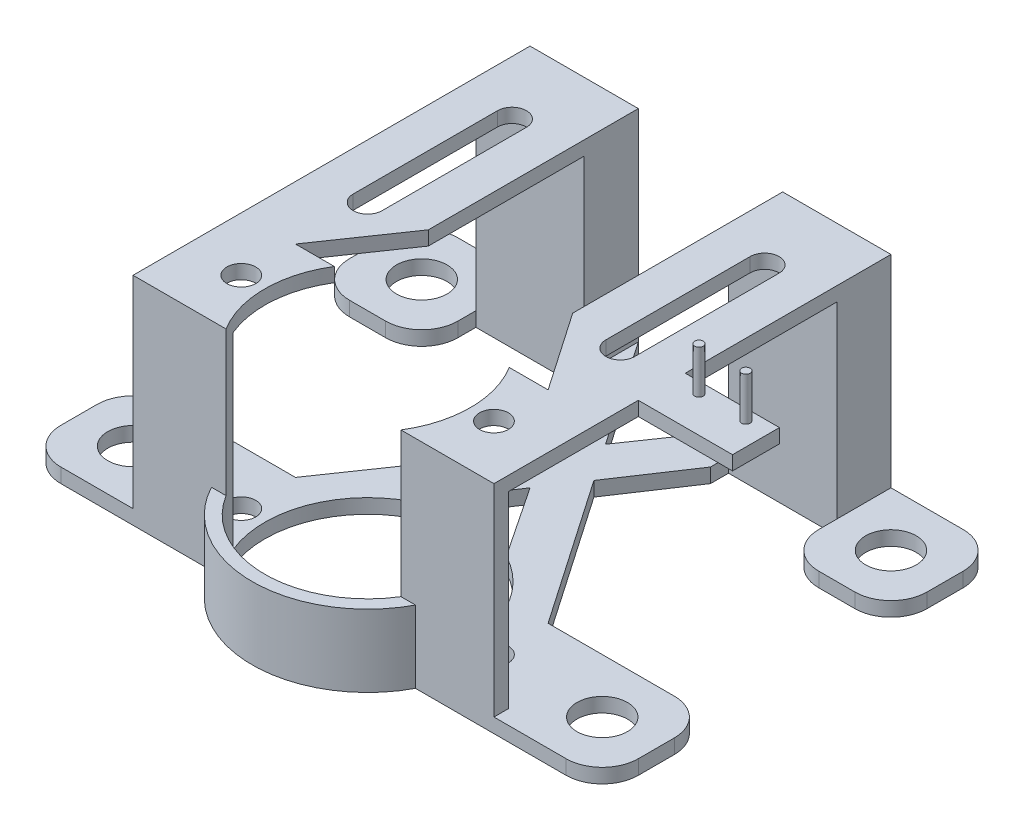
SolidWorks part; units mm, degrees
ref_plane "Front Plane" through (0, 0, 0) normal (0, 0, 1) x (1, 0, 0)
ref_plane "Top Plane" through (0, 0, 0) normal (0, 1, 0) x (1, 0, 0)
ref_plane "Right Plane" through (0, 0, 0) normal (1, 0, 0) x (0, 0, -1)
sketch "Sketch1" plane through (0, 0, 0) normal (0, 1, 0) x (1, 0, 0)
  line L0 (0, 0) -> (-15, 0)
  line L1 (-15, 0) -> (-15, 15)
  line L2 (-15, 15) -> (0, 15)
  line L3 (0, 15) -> (0, 0)
  line L4 (0, 0) -> (20, 0)
  line L5 (20, 0) -> (20, 15)
  line L6 (20, 15) -> (35, 15)
  line L7 (35, 15) -> (35, 0)
  line L8 (35, 0) -> (20, 0)
  line L9 (0, 7.5) -> (20, 7.5)
  line L10 (10, 7.5) -> (27.5, 7.5)
  line L11 (10, 7.5) -> (-7.5, 7.5)
  line L12 (-15, 15) -> (-15, 55)
  line L13 (-15, 55) -> (0, 55)
  line L14 (0, 55) -> (0, 15)
  line L15 (20, 15) -> (20, 55)
  line L16 (20, 55) -> (35, 55)
  line L17 (35, 55) -> (35, 15)
  line L18 (-7.5, 15) -> (-7.5, 25)
  line L19 (27.5, 15) -> (27.5, 25)
  line L20 (-7.5, 55) -> (-7.5, 45)
  line L21 (27.5, 55) -> (27.5, 45)
  line L22 (-7.5, 45) -> (-7.5, 25) construction
  line L23 (-5.5, 45) -> (-5.5, 25)
  line L24 (-9.5, 45) -> (-9.5, 25)
  line L25 (27.5, 45) -> (27.5, 25) construction
  line L26 (29.5, 45) -> (29.5, 25)
  line L27 (25.5, 45) -> (25.5, 25)
  line L28 (35, 0) -> (50, 0)
  line L29 (50, 0) -> (50, 15)
  line L30 (50, 15) -> (35, 15)
  line L31 (-15, 0) -> (-30, 0)
  line L32 (-30, 0) -> (-30, 15)
  line L33 (-30, 15) -> (-15, 15)
  line L34 (-15, 7.5) -> (-30, 7.5)
  line L35 (35, 7.5) -> (50, 7.5)
  line L36 (35, 47.5) -> (50, 47.5)
  line L37 (10, 7.5) -> (39.7, 7.5)
  line L38 (35, 55) -> (50, 55)
  line L39 (50, 55) -> (50, 40)
  line L40 (50, 40) -> (35, 40)
  line L41 (-15, 55) -> (-30, 55)
  line L42 (-30, 55) -> (-30, 40)
  line L43 (-30, 40) -> (-15, 40)
  line L44 (-30, 47.5) -> (-15, 47.5)
  line L45 (39.7, 20) -> (39.7, 15)
  line L46 (39.7, 20) -> (35.25, 20)
  line L47 (35.25, 20) -> (35.25, 26.5)
  line L48 (35.25, 26.5) -> (48.05, 26.5)
  line L49 (48.05, 26.5) -> (48.05, 20)
  line L50 (48.05, 20) -> (39.7, 20)
  line L51 (35.25, 26.5) -> (38.4, 26.5)
  line L52 (38.4, 26.5) -> (38.4, 25)
  line L53 (38.4, 25) -> (44.9, 25)
  line L54 (35.25, 26.5) -> (35, 26.5)
  line L55 (35, 26.5) -> (35, 20)
  line L56 (35, 15) -> (50, 15)
  line L57 (35, 20) -> (35.25, 20)
  line L58 (20, 55) -> (-7.5, 15)
  line L59 (20, 45) -> (0, 15)
  line L60 (0, 55) -> (27.5, 15)
  line L61 (20, 15) -> (0, 45)
  line L62 (0, 45) -> (0, 55)
  line L63 (20, 45) -> (20, 55)
  line L64 (0, 15) -> (-7.5, 15)
  line L65 (20, 15) -> (27.5, 15)
  circle A0 centre (10, 7.5) radius 14.25
  circle A1 centre (-7.5, 7.5) radius 2
  circle A2 centre (27.5, 7.5) radius 2
  arc A3 (-5.5, 45) -> (-9.5, 45) centre (-7.5, 45) ccw
  arc A4 (-9.5, 25) -> (-5.5, 25) centre (-7.5, 25) ccw
  arc A5 (29.5, 45) -> (25.5, 45) centre (27.5, 45) ccw
  arc A6 (25.5, 25) -> (29.5, 25) centre (27.5, 25) ccw
  circle A7 centre (-22.5, 7.5) radius 3.5
  circle A8 centre (42.5, 7.5) radius 3.5
  circle A9 centre (-22.5, 47.5) radius 3.5
  circle A10 centre (42.5, 47.5) radius 3.5
  arc A11 (10, -8.5) -> (24.1333, 0) centre (10, 7.5) ccw
  arc A12 (10, -8.5) -> (-4.1333, 0) centre (10, 7.5) cw
  circle A13 centre (38.4, 25) radius 0.6
  circle A14 centre (44.9, 25) radius 0.6
  point P29 (-7.5, 35)
  point P34 (27.5, 35)
  dimension "D6" = 28.5
  dimension "D10" = 4
  dimension "D11" = 4
  dimension "D18" = 2
  dimension "D19" = 2
  dimension "D22" = 7
  dimension "D23" = 7
  dimension "D28" = 7
  dimension "D29" = 7
  dimension "D30" = 16
  dimension "D38" = 1.2
  dimension "D40" = 1.2
  dimension "D1" = 15
  dimension "D2" = 15
  dimension "D3" = 20
  dimension "D4" = 15
  dimension "D5" = 15
  dimension "D7" = 20
  dimension "D8" = 17.5
  dimension "D9" = 17.5
  dimension "D12" = 40
  dimension "D13" = 40
  dimension "D14" = 10
  dimension "D15" = 10
  dimension "D16" = 10
  dimension "D17" = 10
  dimension "D20" = 15
  dimension "D21" = 15
  dimension "D24" = 15
  dimension "D25" = 15
  dimension "D26" = 15
  dimension "D27" = 15
  dimension "D31" = 29.7
  dimension "D32" = 12.5
  dimension "D33" = 12.8
  dimension "D34" = 6.5
  dimension "D35" = 4.45
  dimension "D36" = 3.15
  dimension "D37" = 1.5
  dimension "D39" = 6.5
  dimension "D41" = 5
extrude "Boss-Extrude3" add sketch "Sketch1" along normal blind 30 contours A4 L18 L2 A0 L14 L13 L20 A3 L23 | A4 L24 A3 L20 L13 L12 L2 L18 | A6 L19 L6 L17 L16 L21 A5 L26 | A6 L27 A5 L21 L16 L15 A0 L6 L19 | A2 A0 L8 L7 L6 | A1 A0 L2 L1 L0 region at (-9.5666, 0, -0.1977) region at (-11.7554, 0, -35) region at (29.4029, 0, -11.6029) region at (-3.3877, 0, -38.1457) region at (31.7554, 0, -35) region at (23.3877, 0, -38.1457)
extrude "Boss-Extrude5" add sketch "Sketch1<6>" along normal blind 2 contours A9 L44 L12 L41 L42 | A9 L44 L42 L43 L12 | A10 L36 L39 L38 L17 | A10 L36 L17 L40 L39 | A8 L35 L29 L30 L7 | A8 L35 L7 L28 L29 | A7 L34 L1 L33 L32 | A7 L34 L32 L31 L1 region at (-22.5, 0, -3.2827) region at (-22.5, 0, -11.7173) region at (42.5, 0, -3.2827) region at (-22.5, 0, -43.2827) region at (42.5, 0, -11.7173) region at (-22.5, 0, -51.7173) region at (42.5, 0, -43.2827) region at (42.5, 0, -51.7173)
sketch "Sketch1<6>" plane through (0, 0, 0) normal (0, 1, 0) x (1, 0, 0) same geometry as "Sketch1"
extrude "Boss-Extrude7" add sketch "Sketch1<8>" along normal blind 30 contours A12 A11 L8 A0 L0 region at (-3.125, 0, 0.2952)
sketch "Sketch1<8>" plane through (0, 0, 0) normal (0, 1, 0) x (1, 0, 0) same geometry as "Sketch1"
extrude "Boss-Extrude8" add sketch "Sketch1<9>" along normal blind 30 contours A2 L37 A0 L8 L7 region at (29.4029, 0, -3.3971)
sketch "Sketch1<9>" plane through (0, 0, 0) normal (0, 1, 0) x (1, 0, 0) same geometry as "Sketch1"
sketch "Sketch6" plane through (0, 0, 0) normal (0, 0, 1) x (1, 0, 0)
  line L0 (-4.1333, 30) -> (24.1333, 30)
  line L1 (24.1333, 30) -> (24.1333, 10)
  line L2 (24.1333, 30) -> (24.1333, 0) construction
  line L3 (24.1333, 10) -> (-4.1333, 10)
  line L4 (-4.1333, 30) -> (-4.1333, 0) construction
  line L5 (-4.1333, 10) -> (-4.1333, 30)
  dimension "D1" = 20
extrude "Cut-Extrude2" cut sketch "Sketch6" along normal blind 9
extrude "Boss-Extrude9" add sketch "Sketch1<11>" along normal blind 36 separate body contours L52 A13 L53 | L53 A13 L52 | A14 region at (44.9, 0, -25.583) region at (38.6546, 0, -25.2546) region at (38.3151, 0, -24.9151)
sketch "Sketch1<11>" plane through (0, 0, 0) normal (0, 1, 0) x (1, 0, 0) same geometry as "Sketch1"
extrude "Boss-Extrude10" add sketch "Sketch1<12>" along normal blind 30 contours L17 L57 L47 L54 | A14 A13 L48 L47 L46 L50 L49 region at (35.125, 0, -23.25) region at (41.65, 0, -23.2011)
sketch "Sketch1<12>" plane through (0, 0, 0) normal (0, 1, 0) x (1, 0, 0) same geometry as "Sketch1"
sketch "Sketch8" plane through (0, 0, -20) normal (0, 0, 1) x (1, 0, 0)
  line L0 (48.05, 30) -> (48.05, 28.0467)
  line L1 (48.05, 30) -> (48.05, 0) construction
  line L2 (48.05, 28.0467) -> (35, 28.0467)
  line L3 (35, 30) -> (35, 0) construction
  line L4 (35, 28.0467) -> (35, 0)
  line L5 (35, 0) -> (48.05, 0)
  line L6 (48.05, 0) -> (48.05, 28.0467)
  line L7 (48.05, 28.0467) -> (48.05, 0)
  line M5 (35, 0) -> (48.05, 0)
  line M6 (48.05, 0) -> (48.05, 30)
  line M8 (35, 30) -> (35, 0)
extrude "Cut-Extrude3" cut sketch "Sketch8" against normal blind 7 contours L2 M6 M8 M5 region at (41.525, 14.0233, -20)
sketch "Sketch10" plane through (35, 0, 0) normal (1, 0, 0) x (0, 0, -1)
  line L0 (15, 2) -> (15, 0)
  line L1 (15, 0) -> (40, 0)
  line L2 (40, 0) -> (47.5, 0)
  line L3 (55, 0) -> (40, 0) construction
  line L4 (47.5, 0) -> (47.5, 28.0467)
  line L5 (47.5, 28.0467) -> (15, 28.0467)
  line L6 (15, 28.0467) -> (15, 2)
extrude "Cut-Extrude8" cut sketch "Sketch10" against normal blind 50
fillet "Fillet2" radius 5 10 edges at (-30, 1, -15) (-30, 1, -40) (-30, 1, -55) (-15, 1, -40) (-30, 1, 0) (50, 1, 0) (50, 1, -15) (35, 1, -40) (50, 1, -40) (50, 1, -55)
sketch "Sketch11" plane through (35, 0, 0) normal (1, 0, 0) x (0, 0, -1)
  line L2 (2.0265, 28.0467) -> (15, 28.0467)
  line L3 (15, 28.0467) -> (15, 2)
  line L4 (15, 2) -> (2.0265, 2)
  line L5 (15, 2) -> (0, 2) construction
  line L6 (2.0265, 2) -> (2.0265, 28.0467)
extrude "Cut-Extrude9" cut sketch "Sketch11" against normal blind 52
extrude "Boss-Extrude11" add sketch "Sketch1<13>" along normal blind 2 contours A0 L14 L58 L2 | A0 L59 L61 L58 L14 | L61 L59 L60 L58 | L58 L60 L59 L15 | L61 L58 L60 L14 | A0 L15 L60 L59 L61 | A0 L65 L60 L15 region at (-2.6415, 0, -18.8542) region at (4.3349, 0, -26.7351) region at (22.6415, 0, -18.8542) region at (15.6651, 0, -26.7351) region at (4.2017, 0, -44.1717) region at (10, 0, -35.2541) region at (15.7983, 0, -44.1717)
sketch "Sketch1<13>" plane through (0, 0, 0) normal (0, 1, 0) x (1, 0, 0) same geometry as "Sketch1"
